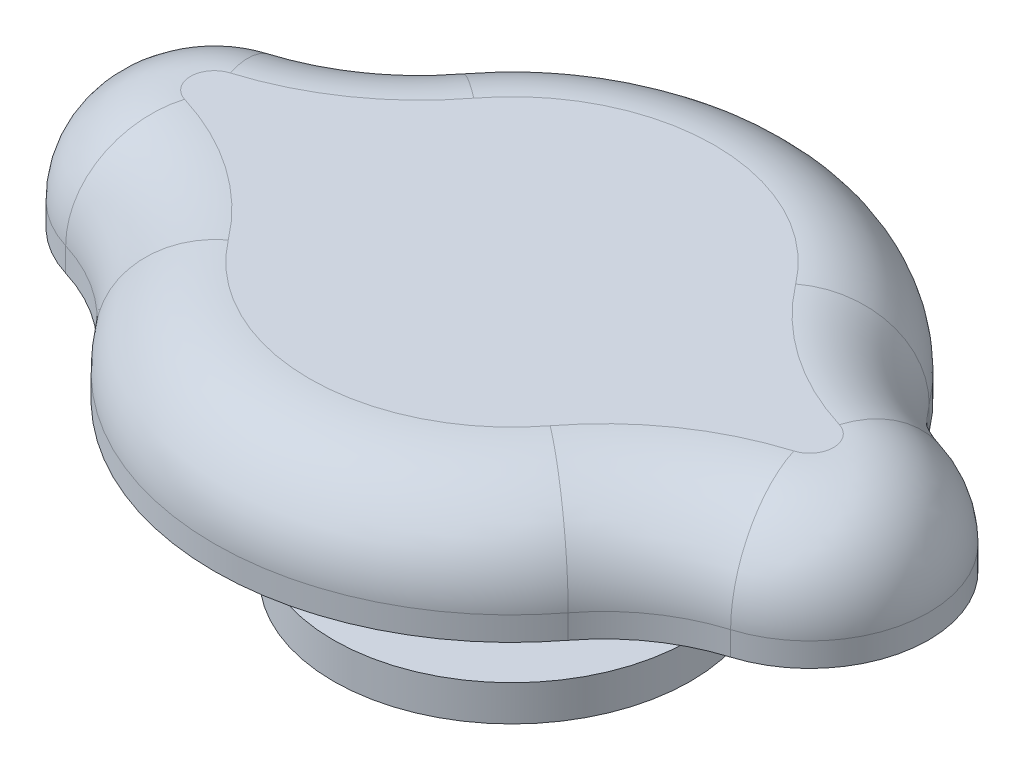
SolidWorks part; units mm, degrees
ref_plane "Front Plane" through (0, 0, 0) normal (0, 0, 1) x (1, 0, 0)
ref_plane "Top Plane" through (0, 0, 0) normal (0, 1, 0) x (1, 0, 0)
ref_plane "Right Plane" through (0, 0, 0) normal (1, 0, 0) x (0, 0, -1)
sketch "Sketch1" plane through (0, 0, 0) normal (0, 1, 0) x (1, 0, 0)
  circle A0 centre (0, 0) radius 9.525
  dimension "D1" = 19.05
extrude "Boss-Extrude1" add sketch "Sketch1" along normal blind 1.27
sketch "Sketch2" plane through (0, 0, 0) normal (0, -1, 0) x (1, 0, 0)
  circle A0 centre (0, 0) radius 9.525
  dimension "D1" = 19.05
extrude "Boss-Extrude3" add sketch "Sketch2" along normal blind 0.635
sketch "Sketch3" plane through (0, -0.635, 0) normal (0, -1, 0) x (1, 0, 0)
  circle A0 centre (0, 0) radius 6.35
  dimension "D1" = 12.7
extrude "Boss-Extrude4" add sketch "Sketch3" along normal blind 0.635
fillet "Fillet1" radius 10.16 1 edges at (0, -1.27, -6.35)
sketch "Sketch4" plane through (0, -1.27, 0) normal (0, -1, 0) x (1, 0, 0)
  circle A0 centre (0, 0) radius 3.175
  dimension "D1" = 6.35
extrude "Boss-Extrude5" add sketch "Sketch4" along normal blind 0.3175
ref_plane "Plane1" through (0, 7.62, 0) normal (0, 1, 0) x (-1, 0, 0)
sketch "Sketch6" plane through (0, 7.62, 0) normal (0, 1, 0) x (-1, 0, 0)
  circle A0 centre (0, 0) radius 15.875
  dimension "D1" = 31.75
extrude "Boss-Extrude7" add sketch "Sketch6" along normal blind 6.35 separate body
sketch "Sketch7" plane through (0, 13.97, 0) normal (0, 1, 0) x (1, 0, 0)
  circle A0 centre (-15.875, 0) radius 6.35
  circle A1 centre (15.875, 0) radius 6.35
  dimension "D1" = 12.7
  dimension "D2" = 12.7
  dimension "D3" = 15.875
  dimension "D4" = 15.875
extrude "Boss-Extrude8" add sketch "Sketch7" against normal blind 6.35
fillet "Fillet2" radius 10.16 4 edges at (14.605, 10.795, -6.2217) (14.605, 10.795, 6.2217) (-14.605, 10.795, -6.2217) (-14.605, 10.795, 6.2217)
fillet "Fillet3" radius 5.08 8 edges at (-14.898, 13.97, 7.4492) (-22.225, 13.97, 0) (-14.898, 13.97, -7.4492) (0, 13.97, -15.875) (14.898, 13.97, -7.4492) (22.225, 13.97, 0) (14.898, 13.97, 7.4492) (0, 13.97, 15.875)
shell "Shell1" thickness 0.635 removed face at (0, 7.62, 0)
sketch "Sketch5" plane through (0, 1.27, 0) normal (0, 1, 0) x (1, 0, 0)
  circle A0 centre (0, 0) radius 3.175
  dimension "D1" = 6.35
extrude "Boss-Extrude9" add sketch "Sketch5" along normal up to surface (12.065 mm away)
sketch "Sketch9" plane through (0, 1.27, 0) normal (0, 1, 0) x (1, 0, 0)
  circle A0 centre (0, 0) radius 7.9375
  dimension "D1" = 15.875
curve "Helix/Spiral1" pitch 5.588 height 11.176 radius 7.9375 left hand yes centre (0, 1.27, 0) axis (0, 1, 0) start towards (0, 0, 1)
sketch "Sketch10" plane through (0, 0, 0) normal (1, 0, 0) x (0, 0, -1)
  circle A0 centre (7.9375, 1.27) radius 0.635
  dimension "D1" = 1.27
sweep "Sweep1" add profiles "Sketch10" path "Helix/Spiral1"
